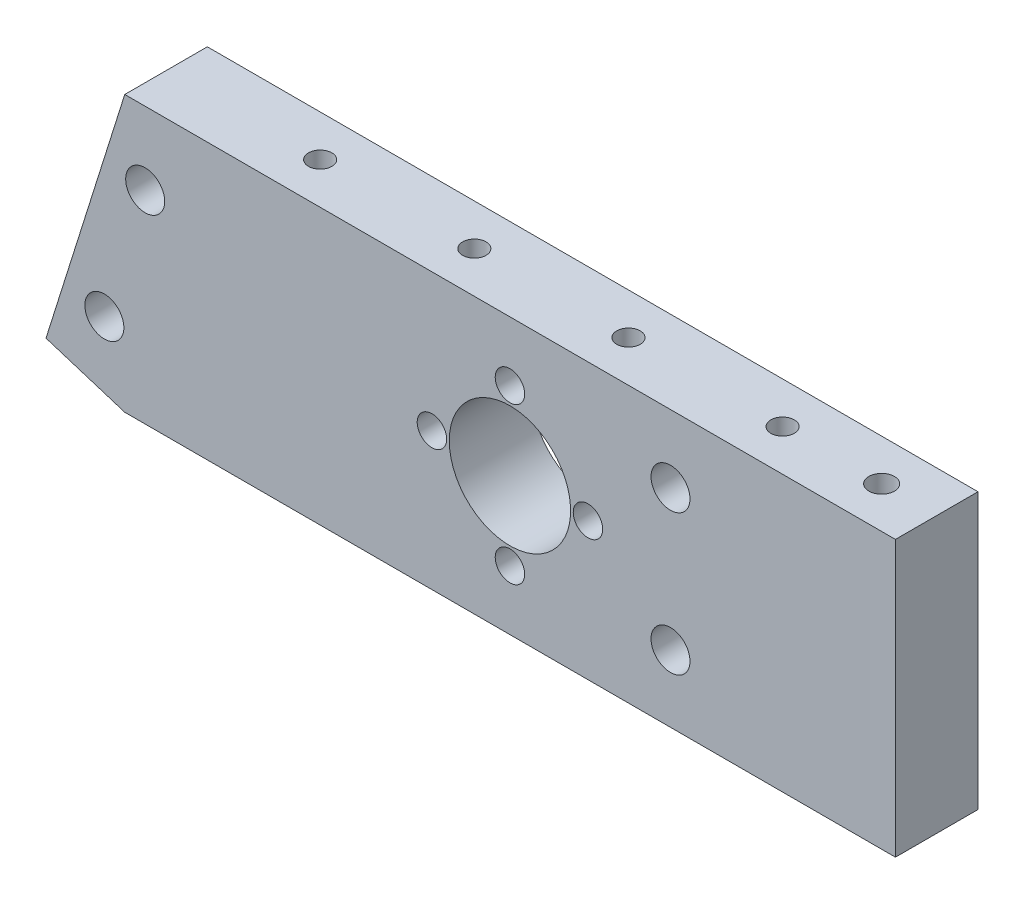
SolidWorks part; units mm, degrees
material "PE High Density"
ref_plane "Front Plane" through (0, 0, 0) normal (0, 0, 1) x (1, 0, 0)
ref_plane "Top Plane" through (0, 0, 0) normal (0, 1, 0) x (1, 0, 0)
ref_plane "Right Plane" through (0, 0, 0) normal (1, 0, 0) x (0, 0, -1)
sketch "Sketch1" plane through (0, 0, 0) normal (0, 0, 1) x (1, 0, 0)
  line L1 (-44.433, 15.875) -> (44.467, 15.875)
  line L3 (-44.433, -15.875) -> (44.467, -15.875)
  line L5 (18.5214, 15.875) -> (18.5214, -15.875) construction
  line L6 (0, 0) -> (44.467, 0) construction
  line L10 (-44.433, 15.875) -> (-53.5192, -13.0175)
  line L12 (0.017, -15.875) -> (0.017, 75.0464) construction
  line L13 (0.017, -15.875) -> (147.1451, -15.875) construction
  line L14 (-44.433, -15.875) -> (-44.433, 15.875) construction
  line L15 (44.467, 15.875) -> (44.467, -15.875)
  line L17 (-44.433, -15.875) -> (-53.5192, -13.0175)
  line L22 (-90.4237, 20.5209) -> (-90.4237, -9.9591) construction
  line L23 (-48.9761, -14.4463) -> (-39.4405, 15.875) construction
  line L25 (-44.433, 15.875) -> (-28.8763, 10.9827) construction
  circle A2 centre (0, 9) radius 1.7 construction
  arc A8 (-5.3578, -2.967) -> (-5.3172, -2.9531) centre (-6.35, 0) ccw construction
  circle A16 centre (0, 0) radius 7 construction
  circle A17 centre (0, 0) radius 9 construction
  circle A18 centre (18.5214, 8.0606) radius 2.2479
  circle A19 centre (18.5211, -8.1496) radius 2.2479
  circle A20 centre (9, 0) radius 1.7 construction
  circle A21 centre (0, -9) radius 1.7 construction
  circle A22 centre (-9, 0) radius 1.7 construction
  circle A23 centre (-90.4237, -2.6566) radius 2.2479 construction
  circle A24 centre (-90.4237, 13.2184) radius 2.2479 construction
  circle A25 centre (-42.0798, 7.4825) radius 2.25
  circle A26 centre (-46.7861, -7.4825) radius 2.25
  circle A27 centre (0, -9) radius 1.7
  circle A28 centre (-9, 0) radius 1.7
  circle A29 centre (0, 9) radius 1.7
  circle A30 centre (9, 0) radius 1.7
  circle A43 centre (0, 0) radius 7
  point P0 (0, 0)
  point P27 (0, 0)
  point P44 (0, 0)
  point P45 (0, 0)
  dimension "D5" = 14
  dimension "D7" = 4.4958
  dimension "D12" = 18.0001
  dimension "D3" = 3.4
  dimension "D20" = 4.4958
  dimension "D21" = 4.4958
  dimension "D23" = 4.5
  dimension "D25" = 4.5
  dimension "D8" = 88.9
  dimension "D17" = 88.9
  dimension "D2" = 90
  dimension "D10" = 31.75
  dimension "D4" = 90
  dimension "D9" = 90
  dimension "D11" = 44.467
  dimension "D13" = 90
  dimension "D15" = 30.48
  dimension "D16" = 7.3025
  dimension "D18" = 7.3025
  dimension "D22" = 90
  dimension "D14" = 9.525
  dimension "D19" = 4.7625
  dimension "D24" = 7.3
  dimension "D26" = 7.3
  dimension "D6" = 4
extrude "Boss-Extrude1" add sketch "Sketch1" along normal blind 9.525
hole_wizard "Tap Drill for #6-32 Tap1" positions "Sketch11" profile "Sketch12" hole size "#6-32" standard "ANSI Inch"
sketch "Sketch11" plane through (0, -15.875, 0) normal (0, -1, 0) x (-1, 0, 0)
  line L0 (-44.467, -9.525) -> (-44.467, 0) construction
  line L1 (44.433, -9.525) -> (-44.467, -9.525) construction
  point P0 (-26.687, -4.7625)
  dimension "D1" = 17.78
  dimension "D2" = 4.7625
sketch "Sketch12" plane through (26.687, -15.875, 4.7625) normal (1, 0, 0) x (0, 0, -1)
  line L0 (0, 0) -> (0, 13.5127)
  line L1 (0, 13.5127) -> (1.3525, 12.7)
  line L2 (1.3525, 12.7) -> (1.3525, 0)
  line L5 (1.3525, 0) -> (0, 0)
  line L10 (0, 13.5127) -> (-1.3526, 12.7) construction
  line L11 (0, -6.35) -> (0, 107.95) construction
  dimension "Hole Dia." = 2.7051
  dimension "Hole Depth" = 12.7
  dimension "Drill Angle" = 118
pattern_linear "LPattern1" count 4 spacing 17.78 along (-1, 0, 0) of "Tap Drill for #6-32 Tap1"
mirror "Mirror8" about plane through (0, 0, 0) normal (0, 1, 0) of "Tap Drill for #6-32 Tap1", "LPattern1"
sketch "Sketch13" plane through (0, -15.875, 0) normal (0, -1, 0) x (1, 0, 0)
  line L0 (38.117, 9.525) -> (38.117, 0) construction
  line L1 (-44.433, 9.525) -> (44.467, 9.525) construction
  line L2 (-44.433, 0) -> (44.467, 0) construction
  line L3 (44.467, 9.525) -> (44.467, 0) construction
  circle A0 centre (38.117, 4.7625) radius 1.4732
  dimension "D2" = 2.9464
  dimension "D1" = 6.35
extrude "Cut-Extrude1" cut sketch "Sketch13" against normal blind 12.7
mirror "Mirror9" about plane through (0, 0, 0) normal (0, 1, 0) of "Cut-Extrude1"
equation "\"Plate Screw Hole Diameter\"= 0.116in"
equation "\"Plate Width\" = 3.5in"
equation "\"Plate Thickness\" = 0.375in"
equation "\"Num holes\" = 4"
equation "\"Plate Height\" = 1.25in"
equation "\"D1@Sketch11\"=\"Plate Width\" / ( \"Num holes\" + 1)"
equation "\"D2@Sketch11\"=\"Plate Thickness\"/2"
equation "\"D3@LPattern1\"=\"Plate Width\" / ( \"Num holes\"  + 1 )"
equation "\"Top Plate Width\" = 4.5in"
equation "\"D8@Sketch1\"=\"Plate Width\""
equation "\"Plate Clearance Hole Diameter\" = 0.125in"
equation "\"Plate Tap Hole Diameter\" = 0.116in"
equation "\"Bottom Plate Length\" = 6.5in"
equation "\"Number Eight Clearance Size\" = 0.177in"
equation "\"D7@Sketch1\"=\"Number Eight Clearance Size\""
equation "\"back_brace_height_offset\"=0.35"
equation "\"D2@Sketch13\"=\"Plate Tap Hole Diameter\""
equation "\"D17@Sketch1\"=\"Plate Width\""
equation "\"D10@Sketch1\"=\"Plate Height\""
